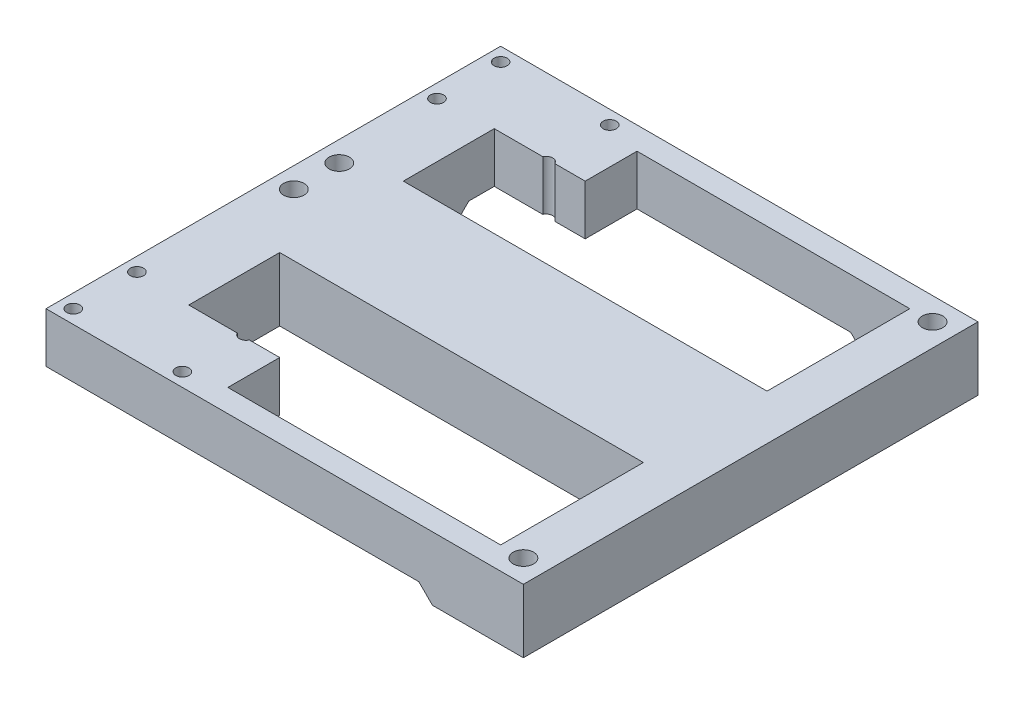
SolidWorks part; units mm, degrees
ref_plane "前视基准面" through (0, 0, 0) normal (0, 0, 1) x (1, 0, 0)
ref_plane "上视基准面" through (0, 0, 0) normal (0, 1, 0) x (1, 0, 0)
ref_plane "右视基准面" through (0, 0, 0) normal (1, 0, 0) x (0, 0, -1)
other "Configuration Table"
sketch "草图1" plane through (0, 0, 0) normal (0, 1, 0) x (1, 0, 0)
  line L1 (0, 0) -> (-105, 0)
  line L2 (0, 0) -> (0, 100)
  line L3 (0, 100) -> (-105, 100)
  line L4 (-105, 0) -> (-105, 100)
  dimension "D1" = 100
  dimension "D2" = 105
extrude "凸台-拉伸1" add sketch "草图1" along normal blind 16
sketch "草图6" plane through (0, 16, 0) normal (0, 1, 0) x (1, 0, 0)
  line L0 (-105, 100) -> (-105, 0) construction
  line L1 (-45.2241, 36.4031) -> (-5, 36.4031)
  line L2 (-70, 16.4031) -> (-70, 5)
  line L3 (-70, 5) -> (-5, 5)
  line L4 (-5, 36.4031) -> (-5, 5)
  line L5 (0, 0) -> (0, 100) construction
  line L6 (-105, 0) -> (0, 0) construction
  line L7 (-105, 50) -> (-60.5255, 50) construction
  line L8 (-70, 95) -> (-5, 95)
  line L9 (-5, 63.5969) -> (-5, 95)
  line L10 (-45.2241, 63.5969) -> (-5, 63.5969)
  line L11 (-70, 83.5969) -> (-70, 95)
  line L12 (-70, 83.5969) -> (-100, 83.5969)
  line L13 (-45.2241, 36.4031) -> (-100, 36.4031)
  line L15 (-70, 16.4031) -> (-100, 16.4031)
  line L16 (-100, 36.4031) -> (-100, 16.4031)
  line L17 (-45.2241, 63.5969) -> (-100, 63.5969)
  line L18 (-100, 63.5969) -> (-100, 83.5969)
  dimension "D1" = 35
  dimension "D2" = 5
  dimension "D3" = 5
  dimension "D4" = 40
  dimension "D5" = 30
  dimension "D6" = 20
extrude "切除-拉伸5" cut sketch "草图6" against normal up to next
sketch "草图8" plane through (0, 16, 0) normal (0, 1, 0) x (1, 0, 0)
  line L0 (-105, 100) -> (-102, 100) construction
  line L1 (0, 100) -> (-105, 100) construction
  line L2 (-102, 100) -> (-102, 97) construction
  line L3 (-102, 97) -> (-78, 97) construction
  line L4 (-78, 97) -> (-78, 83) construction
  line L5 (-78, 83) -> (-102, 83) construction
  line L6 (-105, 50) -> (-51.1245, 50) construction
  line L7 (-105, 100) -> (-105, 0) construction
  line L8 (-78, 17) -> (-102, 17) construction
  line L9 (-78, 3) -> (-78, 17) construction
  line L10 (-102, 3) -> (-78, 3) construction
  line L11 (-102, 0) -> (-102, 3) construction
  line L12 (-105, 0) -> (-102, 0) construction
  circle A0 centre (-102, 97) radius 1.45
  circle A1 centre (-102, 83) radius 1.45
  circle A2 centre (-78, 97) radius 1.45
  circle A3 centre (-78, 83) radius 1.45
  circle A4 centre (-78, 17) radius 1.45
  circle A5 centre (-78, 3) radius 1.45
  circle A6 centre (-102, 17) radius 1.45
  circle A7 centre (-102, 3) radius 1.45
  dimension "D6" = 2.9
  dimension "D7" = 2.9
  dimension "D8" = 2.9
  dimension "D9" = 2.9
  dimension "D1" = 3
  dimension "D2" = 3
  dimension "D3" = 24
  dimension "D4" = 14
  dimension "D5" = 24
extrude "切除-拉伸7" cut sketch "草图8" against normal through all
sketch "草图9" plane through (-5, 0, 0) normal (-1, 0, 0) x (0, 0, 1)
  line L0 (-36.4031, 0) -> (-5, 0) construction
  line L1 (-5, 0) -> (-5, 16) construction
  line L2 (-5, 16) -> (-36.4031, 16) construction
  line L3 (-36.4031, 16) -> (-36.4031, 0) construction
  line L4 (-95, 0) -> (-63.5969, 0) construction
  line L5 (-63.5969, 0) -> (-63.5969, 16) construction
  line L6 (-63.5969, 16) -> (-95, 16) construction
  line L7 (-95, 16) -> (-95, 0) construction
  line L8 (-36.4031, 0) -> (-5, 0)
  line L9 (-5, 0) -> (-5, 16)
  line L10 (-5, 16) -> (-36.4031, 16)
  line L11 (-36.4031, 16) -> (-36.4031, 0)
  line L12 (-95, 0) -> (-63.5969, 0)
  line L13 (-63.5969, 0) -> (-63.5969, 16)
  line L14 (-63.5969, 16) -> (-95, 16)
  line L15 (-95, 16) -> (-95, 0)
extrude "凸台-拉伸2" add sketch "草图9" along normal blind 5
sketch "草图10" plane through (0, 16, 0) normal (0, 1, 0) x (1, 0, 0)
  line L0 (0, 100) -> (0, 95) construction
  line L1 (0, 0) -> (0, 100) construction
  line L2 (0, 95) -> (-5, 95) construction
  line L3 (0, 50) -> (-16.1785, 50) construction
  circle A0 centre (-5, 95) radius 2.25
  circle A1 centre (-5, 5) radius 2.25
  dimension "D3" = 4.5
  dimension "D1" = 5
extrude "切除-拉伸8" cut sketch "草图10" against normal blind 5
sketch "草图11" plane through (0, 0, 0) normal (0, -1, 0) x (1, 0, 0)
  circle A0 centre (-5, -95) radius 2.25 construction
  circle A1 centre (-5, -5) radius 2.25 construction
  circle A2 centre (-5, -95) radius 2.25
  circle A3 centre (-5, -5) radius 2.25
extrude "切除-拉伸9" cut sketch "草图11" against normal blind 7
sketch "草图12" plane through (-100, 0, 0) normal (1, 0, 0) x (0, 0, -1)
  line L0 (16.4031, 0) -> (36.4031, 0) construction
  line L1 (36.4031, 0) -> (36.4031, 16) construction
  line L2 (36.4031, 16) -> (16.4031, 16) construction
  line L3 (16.4031, 16) -> (16.4031, 0) construction
  line L4 (63.5969, 0) -> (83.5969, 0) construction
  line L5 (83.5969, 0) -> (83.5969, 16) construction
  line L6 (83.5969, 16) -> (63.5969, 16) construction
  line L7 (63.5969, 16) -> (63.5969, 0) construction
  line L8 (16.4031, 0) -> (36.4031, 0)
  line L9 (36.4031, 0) -> (36.4031, 16)
  line L10 (36.4031, 16) -> (16.4031, 16)
  line L11 (16.4031, 16) -> (16.4031, 0)
  line L12 (63.5969, 0) -> (83.5969, 0)
  line L13 (83.5969, 0) -> (83.5969, 16)
  line L14 (83.5969, 16) -> (63.5969, 16)
  line L15 (63.5969, 16) -> (63.5969, 0)
extrude "凸台-拉伸3" add sketch "草图12" along normal blind 10
sketch "草图13" plane through (0, 16, 0) normal (0, 1, 0) x (1, 0, 0)
  line L0 (-105, 50) -> (-100.5, 50) construction
  line L1 (-105, 100) -> (-105, 0) construction
  line L3 (-100.5, 50) -> (-100.5, 60) construction
  circle A0 centre (-100.5, 50) radius 2.25
  circle A1 centre (-100.5, 60) radius 2.25
  dimension "D4" = 4.5
  dimension "D5" = 4.5
  dimension "D3" = 10
  dimension "D6" = 4.5
  dimension "D1" = 4.5
  dimension "D2" = 10
extrude "切除-拉伸10" cut sketch "草图13" against normal blind 5
sketch "草图14" plane through (0, 0, 0) normal (0, -1, 0) x (1, 0, 0)
  line L4 (0, -100) -> (0, 0)
  line L5 (0, 0) -> (-105, 0)
  line L6 (-105, 0) -> (-105, -100)
  line L7 (-105, -100) -> (0, -100)
  line L9 (0, 0) -> (-105, 0)
  line L10 (-105, 0) -> (-105, -100)
  line L11 (-105, -100) -> (0, -100)
  line L13 (0, -100) -> (0, 0)
  dimension "D1" = 0
extrude "切除-拉伸11" cut sketch "草图14" against normal blind 2
sketch "草图15" plane through (0, 11, 0) normal (0, 1, 0) x (1, 0, 0)
  circle A0 centre (-5, 5) radius 1.5
  circle A1 centre (-5, 95) radius 1.5
  circle A2 centre (-100.5, 60) radius 1.5
  circle A3 centre (-100.5, 50) radius 1.5
  dimension "D1" = 3
  dimension "D2" = 3
  dimension "D3" = 3
  dimension "D4" = 3
extrude "切除-拉伸12" cut sketch "草图15" against normal blind 4
sketch "草图16" plane through (0, 2, 0) normal (0, -1, 0) x (1, 0, 0)
  line L0 (-10, -36.4031) -> (-10, -5) construction
  line L1 (-105, 0) -> (-20, 0)
  line L2 (-105, 0) -> (-105, -25)
  line L3 (-105, -25) -> (-20, -25)
  line L4 (-20, 0) -> (-20, -25)
  line L5 (-20, -75) -> (-105, -75)
  line L6 (-20, -75) -> (-20, -100)
  line L7 (-20, -100) -> (-105, -100)
  line L8 (-105, -75) -> (-105, -100)
  line L9 (-10, -95) -> (-10, -63.5969) construction
  dimension "D1" = 10
  dimension "D2" = 10
extrude "切除-拉伸13" cut sketch "草图16" against normal blind 3
chamfer "倒角1" distance 3 angle 45 4 edges at (-20, 5, -2.5) (-97.5, 5, -25) (-97.5, 5, -75) (-20, 5, -97.5)
sketch "草图17" plane through (-105, 0, 0) normal (-1, 0, 0) x (0, 0, 1)
  line L0 (0, 9) -> (-55.4, 9) construction
  line L1 (0, 16) -> (0, 5) construction
  line L2 (-100, 16) -> (0, 16) construction
  circle A0 centre (-55.4, 9) radius 2.25
  dimension "D2" = 4.5
  dimension "D1" = 55.4
  dimension "D3" = 7
extrude "切除-拉伸14" cut sketch "草图17" against normal blind 5
sketch "草图18" plane through (-100, 0, 0) normal (-1, 0, 0) x (0, 0, 1)
  circle A0 centre (-55.4, 9) radius 1.5
  dimension "D1" = 3
extrude "切除-拉伸15" cut sketch "草图18" against normal blind 4
